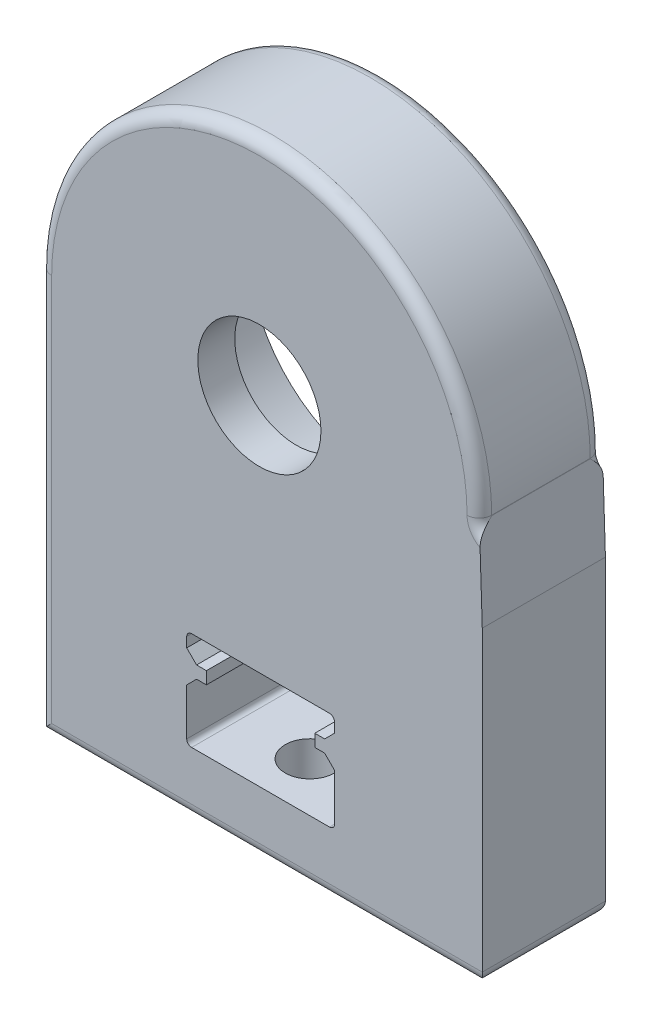
SolidWorks part; units mm, degrees
ref_plane "Front Plane" through (0, 0, 0) normal (0, 0, 1) x (1, 0, 0)
ref_plane "Top Plane" through (0, 0, 0) normal (0, 1, 0) x (1, 0, 0)
ref_plane "Right Plane" through (0, 0, 0) normal (1, 0, 0) x (0, 0, -1)
sketch "Sketch1" plane through (0, 0, 0) normal (0, 0, 1) x (1, 0, 0)
  line L3 (18, 2.5363) -> (18, -9)
  line L4 (18, 14.962) -> (18, 2.5363)
  line L5 (18, 16.1873) -> (18, 14.962)
  line L16 (18, -9) -> (-17.9658, -9)
  line L17 (-17.9658, -9) -> (-17.9658, 23.5)
  line L69 (-4.4, 1) -> (-5.2, 1)
  line L70 (-5.2, 1) -> (-6, 0.2)
  line L71 (-6, 0.2) -> (-6, -3.6)
  line L72 (-5.6, -4) -> (5.6, -4)
  line L73 (6, -3.6) -> (6, 0.2)
  line L74 (6, 0.2) -> (5.2, 1)
  line L75 (5.2, 1) -> (4.4, 1)
  line L76 (4.4, 1) -> (4.4, 2)
  line L77 (4.4, 2) -> (5.2, 2)
  line L78 (5.2, 2) -> (6, 2.8)
  line L79 (6, 2.8) -> (6, 3.6)
  line L80 (5.6, 4) -> (-5.6, 4)
  line L81 (-6, 3.6) -> (-6, 2.8)
  line L82 (-6, 2.8) -> (-5.2, 2)
  line L83 (-5.2, 2) -> (-4.4, 2)
  line L84 (-4.4, 2) -> (-4.4, 1)
  arc A1 (17.7658, 23.5) -> (-17.9658, 23.5) centre (-0.1, 23.5) ccw
  circle A4 centre (-0.1, 23.5) radius 10.9
  arc A19 (-6, -3.6) -> (-5.6, -4) centre (-5.6, -3.6) ccw
  arc A20 (5.6, -4) -> (6, -3.6) centre (5.6, -3.6) ccw
  arc A21 (6, 3.6) -> (5.6, 4) centre (5.6, 3.6) ccw
  arc A22 (-5.6, 4) -> (-6, 3.6) centre (-5.6, 3.6) ccw
  spline S0 degree 1 poles (18, 16.1873) (17.7658, 23.5) knots 0 0 1 1
  dimension "D1" = 21.8
  dimension "D3" = 5
extrude "Boss-Extrude1" add sketch "Sketch1" against normal blind 10
fillet "Fillet5" radius 1 4 edges at (-17.9658, -9, -5) (0.0171, -9, -10) (0.0171, -9, 0) (18, -9, -5)
fillet "Fillet1" radius 1 5 edges at (-17.9658, 7.75, -10) (-17.9658, 7.75, 0) (-0.1, 41.3658, -10) (17.7658, 23.5, -5) (-0.1, 41.3658, 0)
sketch "Sketch3" plane through (0, -9, 0) normal (0, -1, 0) x (1, 0, 0)
  circle A0 centre (0, -4) radius 2
  dimension "D1" = 4
extrude "Cut-Extrude2" cut sketch "Sketch3" against normal blind 8
sketch "Sketch6" plane through (0, 0, 0) normal (0, 0, 1) x (1, 0, 0)
  circle A0 centre (-0.1, 23.5) radius 11.8747
  circle A3 centre (-0.1, 23.5) radius 5
  dimension "D1" = 10
extrude "Boss-Extrude3" add sketch "Sketch6" against normal blind 3
